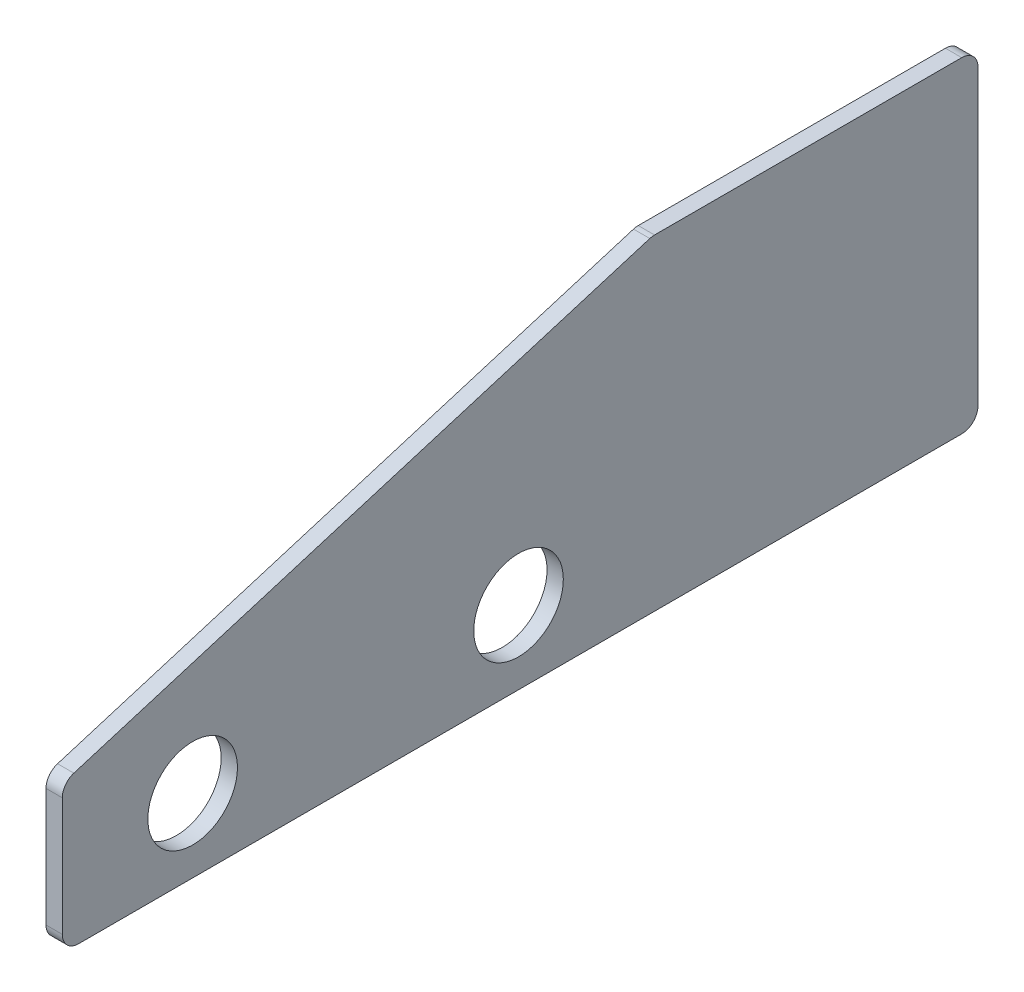
SolidWorks part; units mm, degrees
ref_plane "Front Plane" through (0, 0, 0) normal (0, 0, 1) x (1, 0, 0)
ref_plane "Top Plane" through (0, 0, 0) normal (0, 1, 0) x (1, 0, 0)
ref_plane "Right Plane" through (0, 0, 0) normal (1, 0, 0) x (0, 0, -1)
sketch "Sketch1" plane through (0, 0, 0) normal (1, 0, 0) x (0, 0, -1)
  line L0 (0, 0) -> (56.2, 0)
  line L1 (56.2, 0) -> (56.2, 20)
  line L2 (56.2, 20) -> (36.2, 20)
  line L3 (36.2, 20) -> (0, 9)
  line L4 (0, 9) -> (0, 0)
  dimension "D1" = 20
  dimension "D2" = 9
  dimension "D3" = 20
  dimension "D4" = 56.2
extrude "Boss-Extrude1" add sketch "Sketch1" along normal blind 0.5 and the other way blind 0.5
fillet "Fillet1" radius 1 5 edges at (0, 20, -36.2) (0, 20, -56.2) (0, 0, -56.2) (0, 0, 0) (0, 9, 0)
sketch "Sketch2" plane through (0.5, 0, 0) normal (1, 0, 0) x (0, 0, -1)
  line L0 (0, 8.2587) -> (0, 1) construction
  line L1 (1, 0) -> (55.2, 0) construction
  circle A0 centre (8, 4.5) radius 2.75
  circle A1 centre (28, 4.5) radius 2.75
  point P8 (0, 0)
  dimension "D1" = 5.5
  dimension "D2" = 8
  dimension "D3" = 20
  dimension "D4" = 4.5
extrude "Cut-Extrude1" cut sketch "Sketch2" against normal through all
